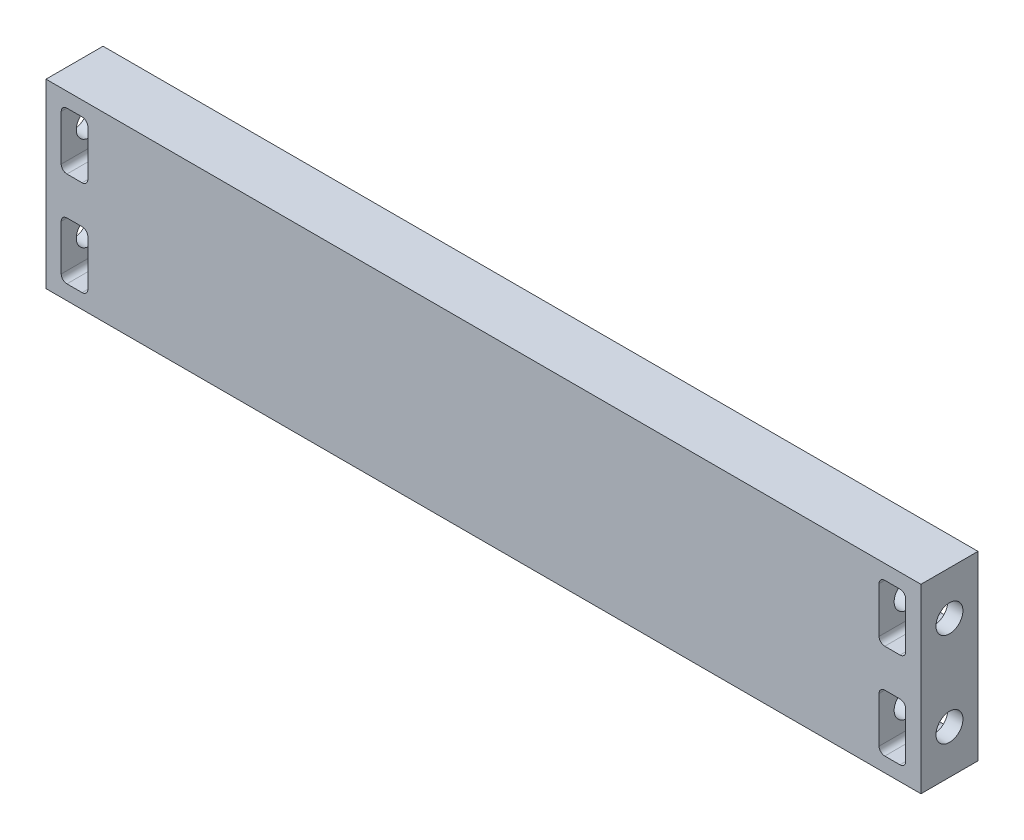
SolidWorks part; units mm, degrees
material "PE High Density"
ref_plane "Front Plane" through (0, 0, 0) normal (0, 0, 1) x (1, 0, 0)
ref_plane "Top Plane" through (0, 0, 0) normal (0, 1, 0) x (1, 0, 0)
ref_plane "Right Plane" through (0, 0, 0) normal (1, 0, 0) x (0, 0, -1)
sketch "Sketch1" plane through (0, 0, 0) normal (0, 0, 1) x (1, 0, 0)
  line L0 (-69.5325, 12.7) -> (-66.9925, 12.7)
  line L1 (-73.025, 15.1438) -> (73.025, 15.1438)
  line L2 (-73.025, 15.1438) -> (-73.025, -15.1438)
  line L3 (-73.025, -15.1438) -> (73.025, -15.1438)
  line L4 (73.025, 15.1438) -> (73.025, -15.1438)
  line L5 (-73.025, 15.1438) -> (73.025, -15.1438) construction
  line L6 (-73.025, -15.1438) -> (73.025, 15.1438) construction
  line L7 (-70.485, 11.7475) -> (-70.485, 4.1275)
  line L8 (-69.5325, 3.175) -> (-66.9925, 3.175)
  line L9 (-66.04, 11.7475) -> (-66.04, 4.1275)
  line L10 (-70.485, 12.7) -> (-66.04, 3.175) construction
  line L11 (-70.485, 3.175) -> (-66.04, 12.7) construction
  line L12 (-68.2625, 15.875) -> (-68.2625, -15.875) construction
  line L13 (-68.2625, 3.175) -> (-68.2625, 11.967) construction
  line L14 (-70.485, 7.9375) -> (-66.04, 7.9375) construction
  line L15 (-73.025, 0) -> (73.025, 0) construction
  line L16 (0, -15.1438) -> (0, 15.1438) construction
  line L17 (-70.485, -7.9375) -> (-66.04, -7.9375) construction
  line L18 (-68.2625, -3.175) -> (-68.2625, -11.967) construction
  line L19 (-70.485, -3.175) -> (-66.04, -12.7) construction
  line L20 (-70.485, -12.7) -> (-66.04, -3.175) construction
  line L21 (-66.04, -11.7475) -> (-66.04, -4.1275)
  line L22 (-69.5325, -3.175) -> (-66.9925, -3.175)
  line L23 (-70.485, -11.7475) -> (-70.485, -4.1275)
  line L24 (-69.5325, -12.7) -> (-66.9925, -12.7)
  line L25 (70.485, 7.9375) -> (66.04, 7.9375) construction
  line L26 (68.2625, 3.175) -> (68.2625, 11.967) construction
  line L27 (70.485, 3.175) -> (66.04, 12.7) construction
  line L28 (70.485, 12.7) -> (66.04, 3.175) construction
  line L29 (66.04, 11.7475) -> (66.04, 4.1275)
  line L30 (69.5325, 3.175) -> (66.9925, 3.175)
  line L31 (70.485, 11.7475) -> (70.485, 4.1275)
  line L32 (69.5325, 12.7) -> (66.9925, 12.7)
  line L33 (70.485, -12.7) -> (66.04, -3.175) construction
  line L34 (70.485, -3.175) -> (66.04, -12.7) construction
  line L35 (68.2625, -3.175) -> (68.2625, -11.967) construction
  line L36 (70.485, -7.9375) -> (66.04, -7.9375) construction
  line L37 (69.5325, -12.7) -> (66.9925, -12.7)
  line L38 (70.485, -11.7475) -> (70.485, -4.1275)
  line L39 (69.5325, -3.175) -> (66.9925, -3.175)
  line L40 (66.04, -11.7475) -> (66.04, -4.1275)
  arc A0 (-66.9925, 3.175) -> (-66.04, 4.1275) centre (-66.9925, 4.1275) ccw
  arc A1 (-66.9925, 12.7) -> (-66.04, 11.7475) centre (-66.9925, 11.7475) cw
  arc A2 (-69.5325, 3.175) -> (-70.485, 4.1275) centre (-69.5325, 4.1275) cw
  arc A3 (-69.5325, 12.7) -> (-70.485, 11.7475) centre (-69.5325, 11.7475) ccw
  arc A4 (-69.5325, -12.7) -> (-70.485, -11.7475) centre (-69.5325, -11.7475) cw
  arc A5 (-69.5325, -3.175) -> (-70.485, -4.1275) centre (-69.5325, -4.1275) ccw
  arc A6 (-66.9925, -12.7) -> (-66.04, -11.7475) centre (-66.9925, -11.7475) ccw
  arc A7 (-66.9925, -3.175) -> (-66.04, -4.1275) centre (-66.9925, -4.1275) cw
  arc A8 (69.5325, 12.7) -> (70.485, 11.7475) centre (69.5325, 11.7475) cw
  arc A9 (69.5325, 3.175) -> (70.485, 4.1275) centre (69.5325, 4.1275) ccw
  arc A10 (66.9925, 12.7) -> (66.04, 11.7475) centre (66.9925, 11.7475) ccw
  arc A11 (66.9925, 3.175) -> (66.04, 4.1275) centre (66.9925, 4.1275) cw
  arc A12 (66.9925, -3.175) -> (66.04, -4.1275) centre (66.9925, -4.1275) ccw
  arc A13 (66.9925, -12.7) -> (66.04, -11.7475) centre (66.9925, -11.7475) cw
  arc A14 (69.5325, -3.175) -> (70.485, -4.1275) centre (69.5325, -4.1275) cw
  arc A15 (69.5325, -12.7) -> (70.485, -11.7475) centre (69.5325, -11.7475) ccw
  point P0 (0, 0)
  point P6 (-68.2625, 7.9375)
  point P53 (-68.2625, -7.9375)
  point P74 (68.2625, 7.9375)
  point P95 (68.2625, -7.9375)
  dimension "D5" = 0.9525
  dimension "D6" = 0.9525
  dimension "D7" = 0.9525
  dimension "D8" = 0.9525
  dimension "D1" = 146.05
  dimension "D2" = 30.2876
  dimension "D3" = 4.445
  dimension "D4" = 9.525
  dimension "D9" = 4.7625
  dimension "D10" = 7.9375
extrude "Boss-Extrude1" add sketch "Sketch1" along normal blind 9.525
sketch "Sketch2" plane through (73.025, 0, 0) normal (1, 0, 0) x (0, 0, -1)
  line L0 (-4.7625, 15.1438) -> (-4.7625, -15.1438) construction
  line L1 (-9.525, 15.1438) -> (0, 15.1438) construction
  line L2 (-9.525, -15.1438) -> (0, -15.1438) construction
  line L3 (-9.525, 0) -> (0, 0) construction
  line L4 (-9.525, -15.1438) -> (-9.525, 15.1438) construction
  circle A0 centre (-4.7625, 7.8438) radius 2.2479
  dimension "D1" = 4.4958
  dimension "D3" = 4.7625
  dimension "D2" = 7.3
extrude "Cut-Extrude1" cut sketch "Sketch2" against normal blind 10.795
mirror "Mirror1" about plane through (0, 0, 0) normal (1, 0, 0) of "Cut-Extrude1" second plane through (0, 0, 0) second plane normal (0, 1, 0)
equation "\"Plate Width\" = 3.5in"
equation "\"Plate Thickness\" = 0.375in"
equation "\"Num holes\" = 4"
equation "\"Plate Height\" = 1.25in"
equation "\"Top Plate Width\" = 4.5in"
equation "\"Plate Clearance Hole Diameter\" = 0.125in"
equation "\"Plate Tap Hole Diameter\" = 0.116in"
equation "\"Bottom Plate Length\" = 6.5in"
equation "\"Number Eight Clearance Size\" = 0.177in"
equation "\"D1@Sketch1\"=\"Bottom Plate Length\" - \"Plate Thickness\" * 2"
equation "\"D2@Sketch1\"=30.28757mm"
equation "\"D9@Sketch1\"=\"Plate Thickness\"/2"
equation "\"D10@Sketch1\"=\"Plate Height\"/4"
equation "\"D1@Boss-Extrude1\"=\"Plate Thickness\""
equation "\"D1@Sketch2\"=\"Number Eight Clearance Size\""
equation "\"D1@Cut-Extrude1\"=0.8 - \"Plate Thickness\""
equation "\"Back Brace Height\" = 1.1962912in"
